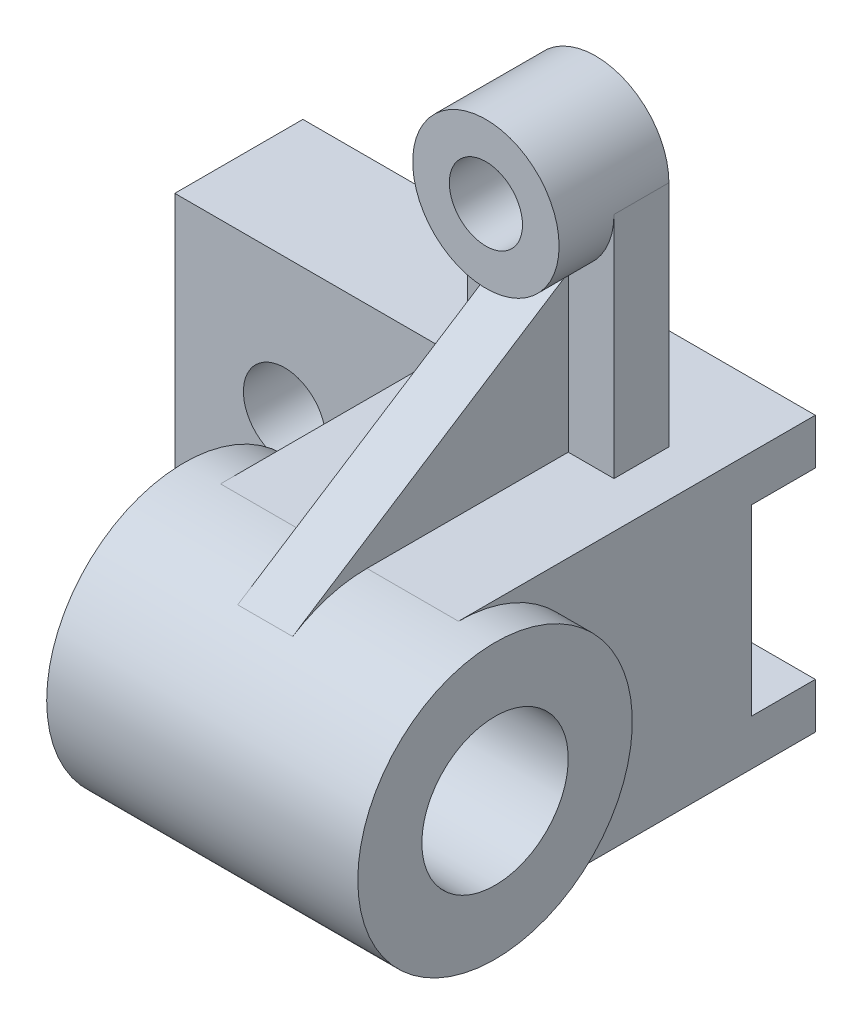
SolidWorks part; units mm, degrees
ref_plane "Front Plane" through (0, 0, 0) normal (0, 0, 1) x (1, 0, 0)
ref_plane "Top Plane" through (0, 0, 0) normal (0, 1, 0) x (1, 0, 0)
ref_plane "Right Plane" through (0, 0, 0) normal (1, 0, 0) x (0, 0, -1)
sketch "Sketch1" plane through (0, 0, 0) normal (0, 0, 1) x (1, 0, 0)
  line L1 (-56, -30) -> (56, -30)
  line L2 (-56, -30) -> (-56, 30)
  line L3 (-56, 30) -> (56, 30)
  line L4 (56, -30) -> (56, 30)
  line L5 (-56, -30) -> (56, 30) construction
  line L6 (-56, 30) -> (56, -30) construction
  point P0 (0, 0)
  dimension "D1" = 112
  dimension "D2" = 60
extrude "Boss-Extrude1" add sketch "Sketch1" against normal blind 28
sketch "Sketch2" plane through (56, 0, 0) normal (1, 0, 0) x (0, 0, -1)
  line L0 (28, -30) -> (28, 30) construction
  line L1 (28, -20) -> (14, -20)
  line L2 (28, -20) -> (28, 20)
  line L3 (28, 20) -> (14, 20)
  line L4 (14, -20) -> (14, 20)
  line L5 (0, -30) -> (0, 30) construction
  dimension "D1" = 40
  dimension "D2" = 10
  dimension "D3" = 14
extrude "Cut-Extrude1" cut sketch "Sketch2" against normal through all
sketch "Sketch3" plane through (0, 0, 0) normal (0, 0, 1) x (1, 0, 0)
  line L0 (56, 30) -> (-56, 30) construction
  line L1 (56, -30) -> (4, -30)
  line L2 (56, -30) -> (56, 30)
  line L3 (56, 30) -> (4, 30)
  line L4 (4, -30) -> (4, 30)
  dimension "D1" = 52
extrude "Boss-Extrude2" add sketch "Sketch3" along normal blind 50
sketch "Sketch4" plane through (4, 0, 0) normal (-1, 0, 0) x (0, 0, 1)
  line L0 (50, 30) -> (50, -30) construction
  circle A0 centre (50, 0) radius 30
  circle A1 centre (50, 0) radius 16
  dimension "D1" = 32
extrude "Boss-Extrude3" add sketch "Sketch4" against normal blind 60 and the other way blind 8
sketch "Sketch5" plane through (4, 0, 0) normal (-1, 0, 0) x (0, 0, 1)
  line L0 (50, 16) -> (50, -16) construction
  circle A0 centre (50, 0) radius 16
extrude "Cut-Extrude2" cut sketch "Sketch5" against normal through all
sketch "Sketch6" plane through (0, 30, 0) normal (0, 1, 0) x (1, 0, 0)
  line L0 (4, 0) -> (56, 0) construction
  line L1 (56, 28) -> (56, -50) construction
  line L3 (46, 6) -> (14, 6)
  line L4 (46, 6) -> (46, -6)
  line L5 (46, -6) -> (14, -6)
  line L6 (14, 6) -> (14, -6)
  line L7 (46, 6) -> (14, -6) construction
  line L8 (46, -6) -> (14, 6) construction
  point P6 (30, 0)
  dimension "D1" = 32
  dimension "D2" = 12
extrude "Boss-Extrude4" add sketch "Sketch6" along normal blind 50
sketch "Sketch8" plane through (0, 0, 6) normal (0, 0, 1) x (1, 0, 0)
  line L0 (14, 80) -> (46, 80) construction
  circle A0 centre (30, 80) radius 16
  circle A1 centre (30, 80) radius 8
  dimension "D1" = 16
extrude "Boss-Extrude5" add sketch "Sketch8" against normal blind 12 and the other way blind 12
sketch "Sketch9" plane through (0, 0, 6) normal (0, 0, 1) x (1, 0, 0)
  line L0 (22, 80) -> (38, 80) construction
  circle A0 centre (30, 80) radius 8
extrude "Cut-Extrude3" cut sketch "Sketch9" against normal through all
ref_plane "Plane2" through (30, 0, 0) normal (1, 0, 0) x (0, 0, -1)
sketch "Sketch17" plane through (30, 0, 0) normal (1, 0, 0) x (0, 0, -1)
  line L0 (-6, 64) -> (-66.2376, 25.2258)
  circle A0 centre (-50, 0) radius 30 construction
rib "Rib1" sketch "Sketch17" sketch "Sketch17" thickness 12 extrusion direction parallel to sketch draft on no parameters "D1"=12
sketch "Sketch18" plane through (0, 0, 0) normal (0, 0, 1) x (1, 0, 0)
  line L0 (-56, 30) -> (-56, -30) construction
  line L1 (4, 30) -> (-56, 30) construction
  circle A0 centre (-32, 0) radius 9
  dimension "D1" = 18
  dimension "D2" = 24
  dimension "D3" = 30
extrude "Cut-Extrude4" cut sketch "Sketch18" against normal through all
